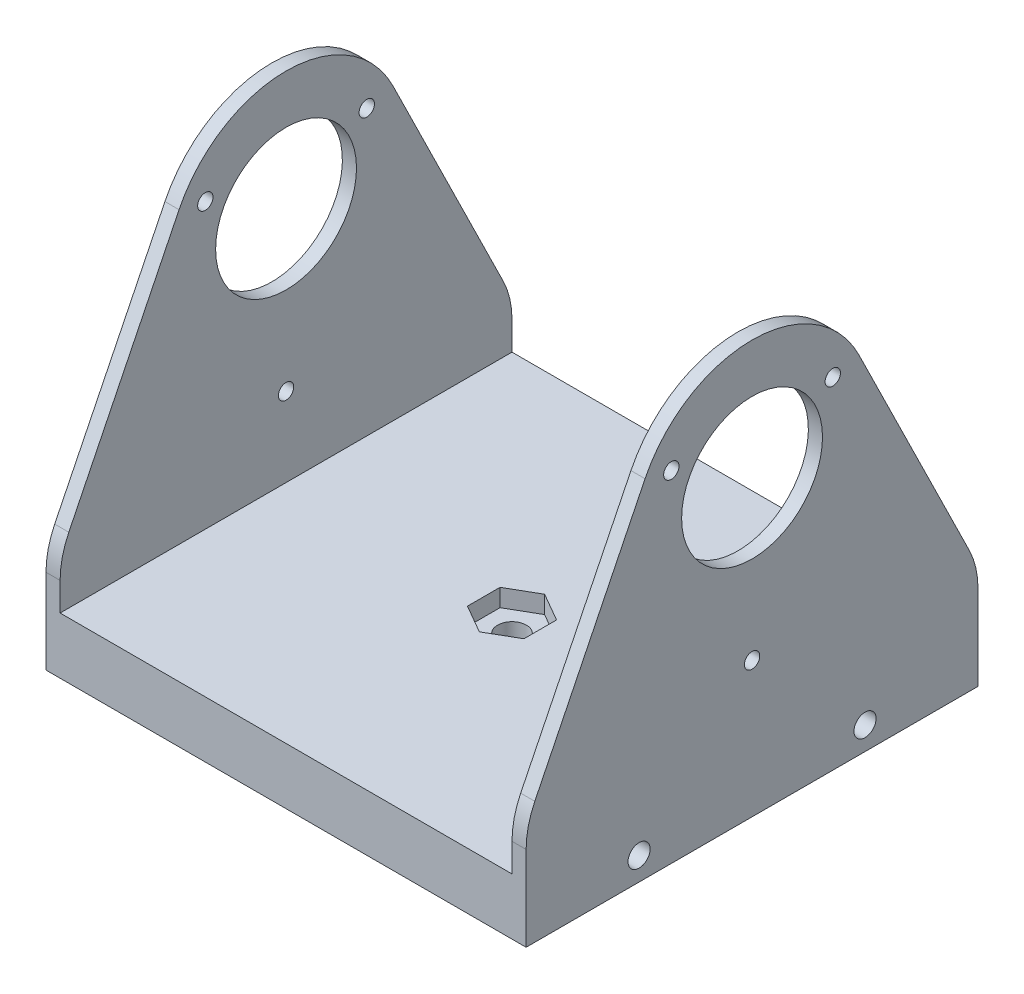
SolidWorks part; units mm, degrees
note: '?' marks a value the reader was unsure of. The reader was unsure of these and kept them because the rebuilt part matched: shared geometry of "Sketch3<4>".
material "ABS"
ref_plane "Front Plane" through (0, 0, 0) normal (0, 0, 1) x (1, 0, 0)
ref_plane "Top Plane" through (0, 0, 0) normal (0, 1, 0) x (1, 0, 0)
ref_plane "Right Plane" through (0, 0, 0) normal (1, 0, 0) x (0, 0, -1)
sketch "Sketch2" plane through (0, 0, 0) normal (0, 0, 1) x (1, 0, 0)
  line L0 (0, 78.74) -> (0, 0)
  line L1 (0, 0) -> (107.95, 0)
  line L2 (107.95, 0) -> (107.95, 78.74)
  line L3 (107.95, 78.74) -> (104.775, 78.74)
  line L4 (104.775, 78.74) -> (104.775, 12.7)
  line L5 (104.775, 12.7) -> (3.175, 12.7)
  line L6 (3.175, 12.7) -> (3.175, 78.74)
  line L7 (3.175, 78.74) -> (0, 78.74)
  dimension "D1" = 107.95
  dimension "D2" = 101.6
  dimension "D3" = 3.175
  dimension "D4" = 12.7
  dimension "D5" = 78.74
extrude "Boss-Extrude1" add sketch "Sketch2" along normal blind 101.6
sketch "Sketch3" plane through (0, 0, 0) normal (-1, 0, 0) x (0, 0, 1)
  line L0 (101.6, 78.74) -> (0, 78.74) construction
  line L1 (0, 78.74) -> (0, 0) construction
  line L2 (101.6, 0) -> (0, 0) construction
  line L3 (101.6, 78.74) -> (101.6, 0) construction
  line L4 (1.9545, 27.4552) -> (26.741, 77.8689)
  line L5 (99.6455, 27.4552) -> (74.859, 77.8689)
  line L6 (101.6, 19.05) -> (101.6, 0)
  line L7 (101.6, 0) -> (0, 0)
  line L8 (0, 0) -> (0, 19.05)
  line L9 (0, 19.05) -> (0, 78.74)
  line L10 (0, 78.74) -> (101.6, 78.74)
  line L11 (101.6, 78.74) -> (101.6, 19.05)
  circle A0 centre (50.8, 66.04) radius 5.8737
  arc A3 (1.9545, 27.4552) -> (0, 19.05) centre (19.05, 19.05) ccw
  arc A4 (101.6, 19.05) -> (99.6455, 27.4552) centre (82.55, 19.05) ccw
  arc A5 (74.859, 77.8689) -> (26.741, 77.8689) centre (50.8, 66.04) ccw
  point P3 (50.8, 78.74)
  point P8 (50.8, 63.5)
  point P22 (62.9451, 67.2131)
  dimension "D1" = 11.7475
  dimension "D3" = 38.1
  dimension "D4" = 53.6194
  dimension "D2" = 12.7
extrude "Cut-Extrude1" cut sketch "Sketch3" against normal through all
extrude "Boss-Extrude3" add sketch "Sketch3<4>" against normal up to surface (3.175 mm away) up to face at (3.175, 60.1663, 50.8)
sketch "Sketch3<4>" plane through (0, 0, 0) normal (-1, 0, 0) x (0, 0, 1) same geometry as "Sketch3"
sketch "Sketch4" plane through (0, 12.7, 0) normal (0, 1, 0) x (1, 0, 0)
  line L1 (60.325, -47.1338) -> (53.975, -43.4677)
  line L2 (53.975, -43.4677) -> (47.625, -47.1338)
  line L3 (47.625, -47.1338) -> (47.625, -54.4662)
  line L4 (47.625, -54.4662) -> (53.975, -58.1323)
  line L5 (53.975, -58.1323) -> (60.325, -54.4662)
  line L6 (60.325, -54.4662) -> (60.325, -47.1338)
  line L7 (104.775, -101.6) -> (3.175, -101.6) construction
  line L8 (104.775, -101.6) -> (104.775, 0) construction
  circle A0 centre (53.975, -50.8) radius 6.35 construction
  point P9 (53.975, -101.6)
  point P17 (104.775, -50.8)
  dimension "D1" = 12.7
extrude "Cut-Extrude2" cut sketch "Sketch4" against normal blind 3.9688
sketch "Sketch5" plane through (0, 8.7312, 0) normal (0, 1, 0) x (1, 0, 0)
  line L0 (47.625, -47.1338) -> (47.625, -54.4662) construction
  circle A0 centre (53.975, -50.8) radius 3.2385
  point P2 (47.625, -50.8)
  dimension "D1" = 6.477
extrude "Cut-Extrude3" cut sketch "Sketch5" against normal through all
sketch "Sketch6" plane through (0, 0, 0) normal (-1, 0, 0) x (0, 0, 1)
  line L0 (32.653, 76.5175) -> (50.8, 30.4808) construction
  line L1 (50.8, 30.4808) -> (68.947, 76.5175) construction
  line L2 (68.947, 76.5175) -> (32.653, 76.5175) construction
  circle A0 centre (32.653, 76.5175) radius 1.7272
  circle A1 centre (68.947, 76.5175) radius 1.7272
  circle A2 centre (50.8, 30.4808) radius 1.7272
  circle A3 centre (50.8, 66.04) radius 5.8737 construction
  circle A4 centre (50.8, 66.04) radius 5.8737 construction
  dimension "D4" = 3.4544
  dimension "D1" = 49.4843
  dimension "D2" = 36.2941
  dimension "D3" = 10.4775
sketch "Sketch7" plane through (107.95, 0, 0) normal (1, 0, 0) x (0, 0, -1)
  circle A3 centre (-50.8, 66.04) radius 26.8097
  circle A4 centre (-50.8, 66.04) radius 5.8737
  dimension "D1" = 53.6194
extrude "Boss-Extrude4" add sketch "Sketch7" against normal up to surface (3.175 mm away) up to face at (104.775, 71.9137, 50.8)
extrude "Cut-Extrude4" cut sketch "Sketch6" against normal through all
sketch "Sketch8" plane through (0, 0, 0) normal (0, -1, 0) x (1, 0, 0)
  line L1 (60.325, 57.15) -> (47.625, 57.15)
  line L2 (60.325, 57.15) -> (60.325, 44.45)
  line L3 (60.325, 44.45) -> (47.625, 44.45)
  line L4 (47.625, 57.15) -> (47.625, 44.45)
  circle A0 centre (53.975, 50.8) radius 3.2385
  circle A1 centre (53.975, 50.8) radius 3.2385 construction
  point P4 (60.325, 50.8)
  point P5 (53.975, 57.15)
  dimension "D1" = 12.7
extrude "Boss-Extrude5" add sketch "Sketch8" along normal blind 12.7
ref_axis "Axis1" through (53.975, -12.7, 50.8) along (0, 1, 0)?
ref_plane "Plane2" through (53.975, 0, 0) normal (1, 0, 0) x (0, 0, -1)
sketch "Sketch9" plane through (53.975, 0, 0) normal (-1, 0, 0) x (0, 0, 1)
  line L1 (101.6, 0) -> (0, 0) construction
  line L5 (44.45, -12.7) -> (44.45, 0)
  line L6 (44.45, 0) -> (31.75, 0)
  line L8 (47.5615, -12.7) -> (44.45, -12.7) construction
  line L9 (44.45, -12.7) -> (41.3385, -12.7)
  line L10 (41.3385, -12.7) -> (31.75, 0)
  dimension "D1" = 12.7
revolve "Revolve1" add sketch "Sketch9" angle 360 about axis through (53.975, -12.7, 50.8) along (0, 1, 0)
sketch "Sketch10" plane through (107.95, 0, 0) normal (1, 0, 0) x (0, 0, -1)
  circle A0 centre (-50.8, 66.04) radius 15.8369
  dimension "D1" = 31.6738
extrude "Cut-Extrude5" cut sketch "Sketch10" against normal through all both and the other way through all
sketch "Sketch13" plane through (0, 0, 0) normal (0, -1, 0) x (1, 0, 0)
  line L0 (107.95, 101.6) -> (107.95, 0) construction
  line L1 (93.2815, 81.7627) -> (88.392, 81.7627)
  line L2 (93.2815, 81.7627) -> (93.2815, 70.6373)
  line L3 (93.2815, 70.6373) -> (88.392, 70.6373)
  line L4 (88.392, 81.7627) -> (88.392, 70.6373)
  line L5 (88.392, 30.9627) -> (93.2815, 30.9627)
  line L6 (88.392, 30.9627) -> (88.392, 19.8373)
  line L7 (88.392, 19.8373) -> (93.2815, 19.8373)
  line L8 (93.2815, 30.9627) -> (93.2815, 19.8373)
  line L9 (107.95, 101.6) -> (107.95, 76.2) construction
  line L10 (107.95, 76.2) -> (107.95, 25.4) construction
  line L11 (107.95, 25.4) -> (107.95, 0) construction
  point P13 (93.2815, 76.2)
  point P17 (93.2815, 25.4)
  dimension "D1" = 4.8895
  dimension "D2" = 11.1255
  dimension "D3" = 19.558
  dimension "D4" = 50.8
extrude "Cut-Extrude7" cut sketch "Sketch13" against normal blind 9.8425
hole_wizard "#10 (0.1935) Diameter Hole1" positions "3DSketch1" profile "Sketch12" hole size "#10" standard "ANSI Inch" end condition up to next
sketch3d "3DSketch1"
  line L0 (107.95, 0, 101.6) -> (107.95, 0, 76.2) construction
  line L1 (107.95, 0, 101.6) -> (107.95, 0, 0) construction
  line L2 (107.95, 0, 76.2) -> (107.95, 0, 25.4) construction
  line L3 (107.95, 0, 25.4) -> (107.95, 0, 0) construction
  line L9 (107.95, 5.207, 76.2) -> (107.95, 0, 76.2) construction
  point P0 (107.95, 5.207, 76.2)
  point P2 (107.95, 5.207, 25.4)
  dimension "D1" = 50.8
  dimension "D2" = 5.207
sketch "Sketch12" plane through (107.95, 5.207, 76.2) normal (0, 1, 0) x (0, 0, -1)
  line L0 (0, 0) -> (0, 88.392)
  line L1 (0, 88.392) -> (2.4828, 88.392)
  line L2 (2.4828, 88.392) -> (2.4828, 0)
  line L5 (2.4828, 0) -> (0, 0)
  line L11 (0, -6.35) -> (0, 107.95) construction
  dimension "Thru Hole Dia." = 4.9657
  dimension "Thru Hole Depth" = 88.392
sketch "Sketch14" plane through (107.95, 0, 0) normal (1, 0, 0) x (0, 0, -1)
  line L0 (-76.2, 0.4445) -> (-76.2, 0) construction
  line L1 (-76.2, 0) -> (-25.4, 0) construction
  line L2 (-101.6, 0) -> (-76.2, 0) construction
  circle A0 centre (-76.2, 5.207) radius 4.7625 construction
  dimension "D1" = 9.525
mirror "Mirror2" about plane through (53.975, 0, 0) normal (1, 0, 0) of "#10 (0.1935) Diameter Hole1", "Cut-Extrude7"
